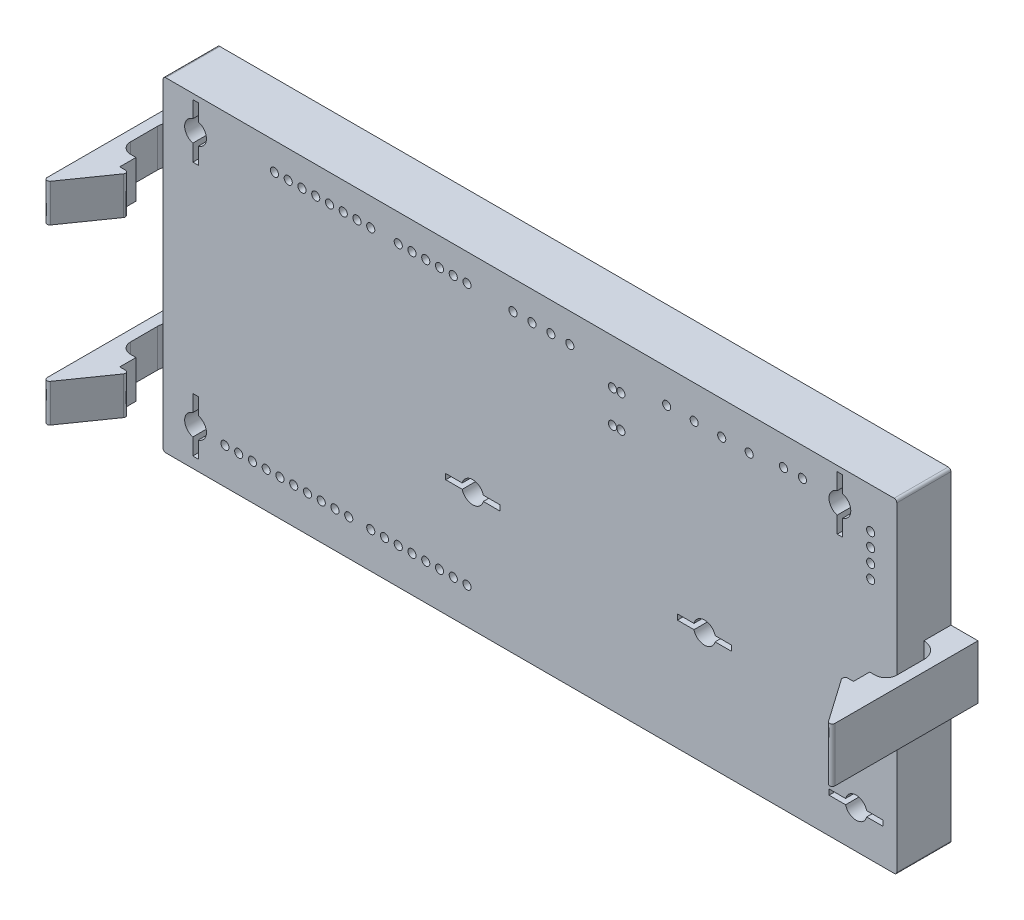
SolidWorks part; units mm, degrees
ref_plane "Front Plane" through (0, 0, 0) normal (0, 0, 1) x (1, 0, 0)
ref_plane "Top Plane" through (0, 0, 0) normal (0, 1, 0) x (1, 0, 0)
ref_plane "Right Plane" through (0, 0, 0) normal (1, 0, 0) x (0, 0, -1)
ref_plane "Plane1" through (0, 0, 0) normal (0, 0, -1) x (-1, 0, 0)
sketch "Sketch1" plane through (0, 0, 0) normal (0, 0, -1) x (-1, 0, 0)
  line L0 (-135.507, -0.5001) -> (-135.5, -59.6)
  line L1 (-135.05, -60) -> (-0.508, -59.9999)
  line L2 (0, -59.5) -> (0, -0.5)
  line L3 (-0.5, 0) -> (-135.007, 0)
  line L4 (-82.775, -8.85) -> (-84.775, -8.85)
  line L5 (-84.775, -7.85) -> (-82.775, -7.85)
  line L6 (-82.775, -14.85) -> (-84.775, -14.85)
  line L7 (-84.775, -13.85) -> (-82.775, -13.85)
  line L8 (-78.575, -10.35) -> (-78.575, -12.35)
  line L9 (-79.575, -12.35) -> (-79.575, -10.35)
  arc A0 (-135.007, 0) -> (-135.507, -0.5001) centre (-135.007, -0.5) ccw
  arc A1 (-135.5, -59.6) -> (-135.05, -60) centre (-135.075, -59.575) ccw
  arc A2 (-0.508, -59.9999) -> (0, -59.5) centre (-0.5, -59.5) ccw
  arc A3 (0, -0.5) -> (-0.5, 0) centre (-0.5, -0.5) ccw
  circle A4 centre (-118.075, -5.3) radius 0.6
  circle A5 centre (-114.575, -5.3) radius 0.6
  circle A6 centre (-108.25, -6.15) radius 0.65
  circle A7 centre (-98.09, -6.15) radius 0.65
  circle A8 centre (-103.17, -6.15) radius 0.65
  circle A9 centre (-93.01, -6.15) radius 0.65
  circle A10 centre (-56.134, -5.08) radius 0.508
  circle A11 centre (-71.625, -5.35) radius 0.6
  circle A12 centre (-68.125, -5.35) radius 0.6
  circle A13 centre (-64.625, -5.35) radius 0.6
  circle A14 centre (-75.125, -5.35) radius 0.6
  circle A15 centre (-102.132, -20.3635) radius 0.1
  circle A16 centre (-102.132, -19.3635) radius 0.1
  circle A17 centre (-102.132, -18.3635) radius 0.1
  arc A18 (-82.775, -7.85) -> (-82.775, -8.85) centre (-82.775, -8.35) cw
  arc A19 (-84.775, -8.85) -> (-84.775, -7.85) centre (-84.775, -8.35) cw
  arc A20 (-84.775, -14.85) -> (-84.775, -13.85) centre (-84.775, -14.35) cw
  arc A21 (-82.775, -13.85) -> (-82.775, -14.85) centre (-82.775, -14.35) cw
  arc A22 (-78.575, -12.35) -> (-79.575, -12.35) centre (-79.075, -12.35) cw
  arc A23 (-79.575, -10.35) -> (-78.575, -10.35) centre (-79.075, -10.35) cw
  circle A24 centre (-103.132, -20.3635) radius 0.1
  circle A25 centre (-103.132, -19.3635) radius 0.1
  circle A26 centre (-103.132, -18.3635) radius 0.1
  circle A27 centre (-104.132, -20.3635) radius 0.1
  circle A28 centre (-104.132, -19.3635) radius 0.1
  circle A29 centre (-104.132, -18.3635) radius 0.1
  circle A30 centre (-100, -39) radius 2
  circle A31 centre (-13.97, -53.34) radius 0.508
  circle A32 centre (-16.51, -53.34) radius 0.508
  circle A33 centre (-19.05, -53.34) radius 0.508
  circle A34 centre (-29.21, -53.34) radius 0.508
  circle A35 centre (-26.67, -53.34) radius 0.508
  circle A36 centre (-24.13, -53.34) radius 0.508
  circle A37 centre (-21.59, -53.34) radius 0.508
  circle A38 centre (-28.194, -5.08) radius 0.508
  circle A39 centre (-25.654, -5.08) radius 0.508
  circle A40 centre (-20.574, -5.08) radius 0.508
  circle A41 centre (-23.114, -5.08) radius 0.508
  circle A42 centre (-45.974, -53.34) radius 0.508
  circle A43 centre (-43.434, -53.34) radius 0.508
  circle A44 centre (-40.894, -53.34) radius 0.508
  circle A45 centre (-34.29, -53.34) radius 0.508
  circle A46 centre (-38.354, -53.34) radius 0.508
  circle A47 centre (-38.354, -5.08) radius 0.508
  circle A48 centre (-43.434, -5.08) radius 0.508
  circle A49 centre (-45.974, -5.08) radius 0.508
  circle A50 centre (-35.814, -5.08) radius 0.508
  circle A51 centre (-33.274, -5.08) radius 0.508
  circle A52 centre (-30.734, -5.08) radius 0.508
  circle A53 centre (-31.75, -53.34) radius 0.508
  circle A54 centre (-53.594, -53.34) radius 0.508
  circle A55 centre (-51.054, -53.34) radius 0.508
  circle A56 centre (-48.514, -53.34) radius 0.508
  circle A57 centre (-53.594, -5.08) radius 0.508
  circle A58 centre (-51.054, -5.08) radius 0.508
  circle A59 centre (-48.514, -5.08) radius 0.508
  circle A60 centre (-56.134, -53.34) radius 0.508
  circle A61 centre (-57.2008, -37.9476) radius 2
  circle A62 centre (-125, -6) radius 2
  circle A63 centre (-128, -53) radius 2
  circle A64 centre (-6, -53) radius 2
  circle A65 centre (-6, -6) radius 2
  circle A66 centre (-11.43, -53.34) radius 0.508
  circle A67 centre (-130.682, -10.04) radius 0.5
  circle A68 centre (-130.682, -7.5) radius 0.5
  circle A69 centre (-130.682, -12.58) radius 0.5
  circle A70 centre (-130.682, -15.12) radius 0.5
extrude "Boss-Extrude1" add sketch "Sketch1" against normal blind 1.6
ref_plane "Plane2" through (0, 0, -5) normal (0, 0, -1) x (-1, 0, 0)
sketch "Sketch4" plane through (0, 0, -5) normal (0, 0, -1) x (-1, 0, 0)
  line L0 (-82.275, -14.35) -> (-85.275, -14.35) construction
  line L1 (-82.275, -8.35) -> (-85.275, -8.35) construction
  line L8 (-135.507, -0.5001) -> (-135.5, -59.6)
  line L9 (-135.05, -60) -> (-0.508, -59.9999)
  line L10 (0, -59.5) -> (0, -0.5)
  line L11 (-0.5, 0) -> (-135.007, 0)
  line L12 (-135.507, -0.5001) -> (-135.5, -59.6)
  line L13 (-135.05, -60) -> (-0.508, -59.9999)
  line L14 (0, -59.5) -> (0, -0.5)
  line L15 (-0.5, 0) -> (-135.007, 0)
  circle A0 centre (-11.43, -53.34) radius 0.75
  circle A3 centre (-13.97, -53.34) radius 0.75
  circle A5 centre (-16.51, -53.34) radius 0.75
  circle A7 centre (-19.05, -53.34) radius 0.75
  circle A9 centre (-21.59, -53.34) radius 0.75
  circle A11 centre (-24.13, -53.34) radius 0.75
  circle A13 centre (-26.67, -53.34) radius 0.75
  circle A15 centre (-29.21, -53.34) radius 0.75
  circle A17 centre (-31.75, -53.34) radius 0.75
  circle A19 centre (-34.29, -53.34) radius 0.75
  circle A21 centre (-38.354, -53.34) radius 0.75
  circle A23 centre (-40.894, -53.34) radius 0.75
  circle A25 centre (-43.434, -53.34) radius 0.75
  circle A27 centre (-45.974, -53.34) radius 0.75
  circle A29 centre (-48.514, -53.34) radius 0.75
  circle A30 centre (-51.054, -53.34) radius 0.75
  circle A31 centre (-53.594, -53.34) radius 0.75
  circle A34 centre (-56.134, -53.34) radius 0.75
  circle A35 centre (-20.574, -5.08) radius 0.75
  circle A38 centre (-23.114, -5.08) radius 0.75
  circle A39 centre (-25.654, -5.08) radius 0.75
  circle A43 centre (-28.194, -5.08) radius 0.75
  circle A45 centre (-30.734, -5.08) radius 0.75
  circle A47 centre (-33.274, -5.08) radius 0.75
  circle A49 centre (-35.814, -5.08) radius 0.75
  circle A51 centre (-38.354, -5.08) radius 0.75
  circle A53 centre (-125, -6) radius 2.0125
  circle A55 centre (-43.434, -5.08) radius 0.75
  circle A57 centre (-45.974, -5.08) radius 0.75
  circle A59 centre (-48.514, -5.08) radius 0.75
  circle A61 centre (-51.054, -5.08) radius 0.75
  circle A63 centre (-53.594, -5.08) radius 0.75
  circle A65 centre (-56.134, -5.08) radius 0.75
  circle A67 centre (-64.625, -5.35) radius 0.75
  circle A69 centre (-68.125, -5.35) radius 0.75
  circle A71 centre (-71.625, -5.35) radius 0.75
  circle A73 centre (-75.125, -5.35) radius 0.75
  arc A75 (-82.775, -14.85) -> (-82.775, -13.85) centre (-82.775, -14.35) ccw construction
  arc A77 (-84.775, -13.85) -> (-84.775, -14.85) centre (-84.775, -14.35) ccw construction
  circle A79 centre (-100, -39) radius 2.0125
  circle A81 centre (-128, -53) radius 2.0125
  arc A83 (-82.775, -8.85) -> (-82.775, -7.85) centre (-82.775, -8.35) ccw construction
  arc A85 (-84.775, -7.85) -> (-84.775, -8.85) centre (-84.775, -8.35) ccw construction
  circle A87 centre (-83, -8.35) radius 0.75
  circle A89 centre (-84.55, -8.35) radius 0.75
  circle A91 centre (-83, -14.35) radius 0.75
  circle A93 centre (-84.55, -14.35) radius 0.75
  circle A95 centre (-93.01, -6.15) radius 0.75
  circle A97 centre (-98.09, -6.15) radius 0.75
  circle A99 centre (-103.17, -6.15) radius 0.75
  circle A101 centre (-108.25, -6.15) radius 0.75
  circle A103 centre (-114.575, -5.3) radius 0.75
  circle A105 centre (-118.075, -5.3) radius 0.75
  circle A107 centre (-130.682, -15.12) radius 0.75
  circle A109 centre (-130.682, -12.58) radius 0.75
  circle A111 centre (-130.682, -10.04) radius 0.75
  circle A113 centre (-130.682, -7.5) radius 0.75
  circle A115 centre (-57.2008, -37.9476) radius 2.0125
  circle A117 centre (-6, -53) radius 2.0125
  circle A119 centre (-6, -6) radius 2.0125
  arc A128 (-135.007, 0) -> (-135.507, -0.5001) centre (-135.007, -0.5) ccw
  arc A129 (-135.5, -59.6) -> (-135.05, -60) centre (-135.075, -59.575) ccw
  arc A130 (-0.508, -59.9999) -> (0, -59.5) centre (-0.5, -59.5) ccw
  arc A131 (0, -0.5) -> (-0.5, 0) centre (-0.5, -0.5) ccw
  arc A132 (-135.007, 0) -> (-135.507, -0.5001) centre (-135.007, -0.5) ccw
  arc A133 (-135.5, -59.6) -> (-135.05, -60) centre (-135.075, -59.575) ccw
  arc A134 (-0.508, -59.9999) -> (0, -59.5) centre (-0.5, -59.5) ccw
  arc A135 (0, -0.5) -> (-0.5, 0) centre (-0.5, -0.5) ccw
  point P119 (-83.775, -14.35)
  dimension "D1" = 1.5
  dimension "D3" = 1.5
  dimension "D2" = 4.025
  dimension "D4" = 1.55
  dimension "D6" = 0.775
  dimension "D7" = 0
extrude "Boss-Extrude2" add sketch "Sketch4" along normal blind 10 separate body contours L14 A135 L15 A132 L12 A133 L13 A134 A0 A3 A5 A7 A9 A11 A13 A15 A17 A19 A21 A23 A25 A27 A29 A30 A31 A34 A35 A38 A39 | A119 | A117 | A115 | A79 | A81 | A53 region at (67.832, -30.0472, -5)
extrude "Cut-Extrude1" cut sketch "Sketch4<5>" along normal blind 5 contours A53 | A81 | A79 | A115 | A117 | A119 region at (125, -6, -5) region at (100, -39, -5) region at (128, -53, -5) region at (57.2008, -37.9476, -5) region at (6, -53, -5) region at (6, -6, -5)
sketch "Sketch4<5>" plane through (0, 0, -5) normal (0, 0, -1) x (-1, 0, 0) same geometry as "Sketch4"
sketch "Sketch8" plane through (0, 0, -15) normal (0, 0, -1) x (-1, 0, 0)
  circle A0 centre (-6, -6) radius 2 construction
  circle A1 centre (-6, -53) radius 2 construction
  circle A2 centre (-57.2008, -37.9476) radius 2 construction
  circle A3 centre (-100, -39) radius 2 construction
  circle A4 centre (-125, -6) radius 2 construction
  circle A5 centre (-128, -53) radius 2 construction
  circle A6 centre (-6, -6) radius 2
  circle A7 centre (-6, -53) radius 2
  circle A8 centre (-57.2008, -37.9476) radius 2
  circle A9 centre (-100, -39) radius 2
  circle A10 centre (-125, -6) radius 2
  circle A11 centre (-128, -53) radius 2
  circle A12 centre (-128, -53) radius 1.475
  circle A13 centre (-125, -6) radius 1.475
  circle A14 centre (-100, -39) radius 1.475
  circle A15 centre (-57.2008, -37.9476) radius 1.475
  circle A16 centre (-6, -53) radius 1.475
  circle A17 centre (-6, -6) radius 1.475
  dimension "D1" = 2.95
delete or keep bodies "Body-Delete/Keep 1" type delete bodies bodies 103
sketch "Sketch5" plane through (0, 0, -5) normal (0, 0, 1) x (1, 0, 0)
  line L1 (133, -52.5) -> (123, -52.5)
  line L2 (133, -52.5) -> (133, -53.5)
  line L3 (133, -53.5) -> (123, -53.5)
  line L4 (123, -52.5) -> (123, -53.5)
  line L5 (133, -52.5) -> (123, -53.5) construction
  line L6 (133, -53.5) -> (123, -52.5) construction
  line L7 (125.5, -1) -> (124.5, -1)
  line L8 (125.5, -1) -> (125.5, -11)
  line L9 (125.5, -11) -> (124.5, -11)
  line L10 (124.5, -1) -> (124.5, -11)
  line L11 (125.5, -1) -> (124.5, -11) construction
  line L12 (125.5, -11) -> (124.5, -1) construction
  line L13 (105, -38.5) -> (95, -38.5)
  line L14 (105, -38.5) -> (105, -39.5)
  line L15 (105, -39.5) -> (95, -39.5)
  line L16 (95, -38.5) -> (95, -39.5)
  line L17 (105, -38.5) -> (95, -39.5) construction
  line L18 (105, -39.5) -> (95, -38.5) construction
  line L19 (62.2008, -38.4476) -> (52.2008, -38.4476)
  line L20 (62.2008, -38.4476) -> (62.2008, -37.4476)
  line L21 (62.2008, -37.4476) -> (52.2008, -37.4476)
  line L22 (52.2008, -38.4476) -> (52.2008, -37.4476)
  line L23 (62.2008, -38.4476) -> (52.2008, -37.4476) construction
  line L24 (62.2008, -37.4476) -> (52.2008, -38.4476) construction
  line L25 (6.5, -48) -> (5.5, -48)
  line L26 (6.5, -48) -> (6.5, -58)
  line L27 (6.5, -58) -> (5.5, -58)
  line L28 (5.5, -48) -> (5.5, -58)
  line L29 (6.5, -48) -> (5.5, -58) construction
  line L30 (6.5, -58) -> (5.5, -48) construction
  line L31 (6.5, -1) -> (5.5, -1)
  line L32 (6.5, -1) -> (6.5, -11)
  line L33 (6.5, -11) -> (5.5, -11)
  line L34 (5.5, -1) -> (5.5, -11)
  line L35 (6.5, -1) -> (5.5, -11) construction
  line L36 (6.5, -11) -> (5.5, -1) construction
  point P0 (128, -53)
  point P6 (125, -6)
  point P12 (100, -39)
  point P18 (57.2008, -37.9476)
  point P24 (6, -53)
  point P30 (6, -6)
  dimension "D1" = 10
  dimension "D2" = 1
  dimension "D3" = 10
  dimension "D4" = 1
  dimension "D5" = 10
  dimension "D6" = 1
  dimension "D7" = 10
  dimension "D8" = 1
  dimension "D9" = 1
  dimension "D10" = 10
  dimension "D11" = 1
  dimension "D12" = 10
extrude "Cut-Extrude2" cut sketch "Sketch5" against normal blind 6
extrude "Cut-Extrude3" cut sketch "Sketch8" against normal blind 7 contours A17 | A16 | A15 | A14 | A12 | A13 region at (128, -53, -15) region at (125, -6, -15) region at (100, -39, -15) region at (57.2008, -37.9476, -15) region at (6, -53, -15) region at (6, -6, -15)
sketch "Sketch9" plane through (0, 0, -15) normal (0, 0, -1) x (-1, 0, 0)
  line L0 (0, -59.5) -> (0, -0.5) construction
  line L1 (0, -10.5) -> (5, -10.5)
  line L2 (0, -10.5) -> (0, -17.5)
  line L3 (0, -17.5) -> (5, -17.5)
  line L4 (5, -10.5) -> (5, -17.5)
  line L5 (5, -17.5) -> (5, -42.5) construction
  line L6 (0, -42.5) -> (5, -42.5)
  line L7 (0, -42.5) -> (0, -49.5)
  line L8 (0, -49.5) -> (5, -49.5)
  line L9 (5, -42.5) -> (5, -49.5)
  line L10 (-135.507, -0.5001) -> (-135.5, -59.6) construction
  line L12 (-135.5041, -25.05) -> (-140.5041, -25.05)
  line L13 (-135.5041, -25.05) -> (-135.5041, -35.05)
  line L14 (-135.5041, -35.05) -> (-140.5041, -35.05)
  line L15 (-140.5041, -25.05) -> (-140.5041, -35.05)
  line L16 (5, -10.5) -> (3, -10.5)
  line L17 (5, -10.5) -> (5, -17.5)
  line L18 (5, -17.5) -> (3, -17.5)
  line L19 (3, -10.5) -> (3, -17.5)
  line L20 (5, -42.5) -> (3, -42.5)
  line L21 (5, -42.5) -> (5, -49.5)
  line L22 (5, -49.5) -> (3, -49.5)
  line L23 (3, -42.5) -> (3, -49.5)
  line L24 (-140.5041, -25.05) -> (-138.5041, -25.05)
  line L25 (-140.5041, -25.05) -> (-140.5041, -35.05)
  line L26 (-140.5041, -35.05) -> (-138.5041, -35.05)
  line L27 (-138.5041, -25.05) -> (-138.5041, -35.05)
  point P10 (0, -30)
  point P11 (5, -30)
  point P18 (-135.5041, -30.05)
  point P19 (-135.5035, -30.05)
  dimension "D1" = 5
  dimension "D2" = 7
  dimension "D3" = 2
  dimension "D4" = 25
  dimension "D5" = 5
  dimension "D6" = 10
  dimension "D7" = 2
  dimension "D8" = 2
extrude "Boss-Extrude3" add sketch "Sketch9" against normal blind 5 contours L23 L6 L7 L8 | L6 L23 L8 L9 | L19 L1 L2 L3 | L1 L19 L3 L4 | L27 L12 L15 L14 | L12 L27 L14 L13 region at (-1.5, -14, -15) region at (-4, -14, -15) region at (-1.5, -46, -15) region at (-4, -46, -15) region at (137.0041, -30.05, -15) region at (139.5041, -30.05, -15)
extrude "Boss-Extrude4" add sketch "Sketch9<3>" against normal blind 13 from surface contours L1 L19 L3 L4 | L6 L23 L8 L9 | L27 L12 L15 L14 region at (-4, -14, -15) region at (-4, -46, -15) region at (139.5041, -30.05, -15) starting at face at (138.0041, -30.05, -10)
sketch "Sketch9<3>" plane through (0, 0, -15) normal (0, 0, -1) x (-1, 0, 0) same geometry as "Sketch9"
sketch "Sketch10" plane through (0, 0, 0) normal (0, 1, 0) x (1, 0, 0)
  line L0 (140.5041, -3) -> (133.507, -3)
  line L1 (133.507, -3) -> (140.5041, -13)
  line L2 (140.5041, -13) -> (140.5041, -3)
  line L3 (135.507, 15) -> (135.507, 5) construction
  line L4 (-5, -3) -> (2, -3)
  line L5 (2, -3) -> (-5, -13)
  line L6 (-5, -13) -> (-5, -3)
  line L7 (0, 15) -> (0, 5) construction
  dimension "D1" = 2
  dimension "D2" = 10
  dimension "D3" = 2
  dimension "D4" = 10
extrude "Boss-Extrude5" add sketch "Sketch10" against normal up to surface (35.05 mm away) from surface contours L1 L2 L0 region at (138.1717, 0, 6.3333) up to face at (138.1708, -35.05, -7.3333) starting at face at (138.1708, -25.05, -7.3333)
extrude "Boss-Extrude6" add sketch "Sketch10<3>" against normal up to surface (17.5 mm away) from surface contours L6 L5 L4 region at (-2.6667, 0, 6.3333) up to face at (-2.6667, -17.5, -7.3333) starting at face at (-2.6667, -10.5, -7.3333)
sketch "Sketch10<3>" plane through (0, 0, 0) normal (0, 1, 0) x (1, 0, 0) same geometry as "Sketch10"
extrude "Boss-Extrude7" add sketch "Sketch10<4>" along normal up to surface (-42.5 mm away) from surface contours L6 L5 L4 region at (-2.6667, 0, 6.3333) up to face at (-2.6667, -42.5, -7.3333) starting at face at (-2.6667, -49.5, -7.3333)
sketch "Sketch10<4>" plane through (0, 0, 0) normal (0, 1, 0) x (1, 0, 0) same geometry as "Sketch10"
fillet "Fillet1" radius 0.5 2 edges at (133.507, -30.05, 3) (140.5041, -30.05, 13)
fillet "Fillet2" radius 0.5 4 edges at (2, -14, 3) (-5, -14, 13) (-5, -46, 13) (2, -46, 3)
extrude "Boss-Extrude8" add sketch "Sketch9<4>" along normal blind 3 from surface contours L19 L1 L2 L3 | L23 L6 L7 L8 region at (-1.5, -14, -15) region at (-1.5, -46, -15) starting at face at (-0.9802, -14, 3)
sketch "Sketch9<4>" plane through (0, 0, -15) normal (0, 0, -1) x (-1, 0, 0) same geometry as "Sketch9"
extrude "Boss-Extrude9" add sketch "Sketch9<5>" along normal blind 3 from surface contours L12 L27 L14 L13 region at (137.0041, -30.05, -15) starting at face at (136.4856, -30.05, 3)
sketch "Sketch9<5>" plane through (0, 0, -15) normal (0, 0, -1) x (-1, 0, 0) same geometry as "Sketch9"
fillet "Fillet3" radius 3 2 edges at (-3, -14, -10) (-3, -46, -10)
fillet "Fillet4" radius 3 1 edges at (138.5041, -30.05, -10)
fillet "Fillet5" radius 2 1 edges at (138.5041, -30.05, 0)
fillet "Fillet6" radius 2 2 edges at (-3, -14, 0) (-3, -46, 0)
equation "\"POGO_SNUG_DIA\"= 1.5"
equation "\"D1@Sketch4\"=\"POGO_SNUG_DIA\""
equation "\"POGO_TIGHT_DIA\"= 1.5"
equation "\"D3@Sketch4\"=\"POGO_TIGHT_DIA\""
equation "\"GUIDE_PIN_DIA\"=4.025"
equation "\"D2@Sketch4\"=\"GUIDE_PIN_DIA\""
